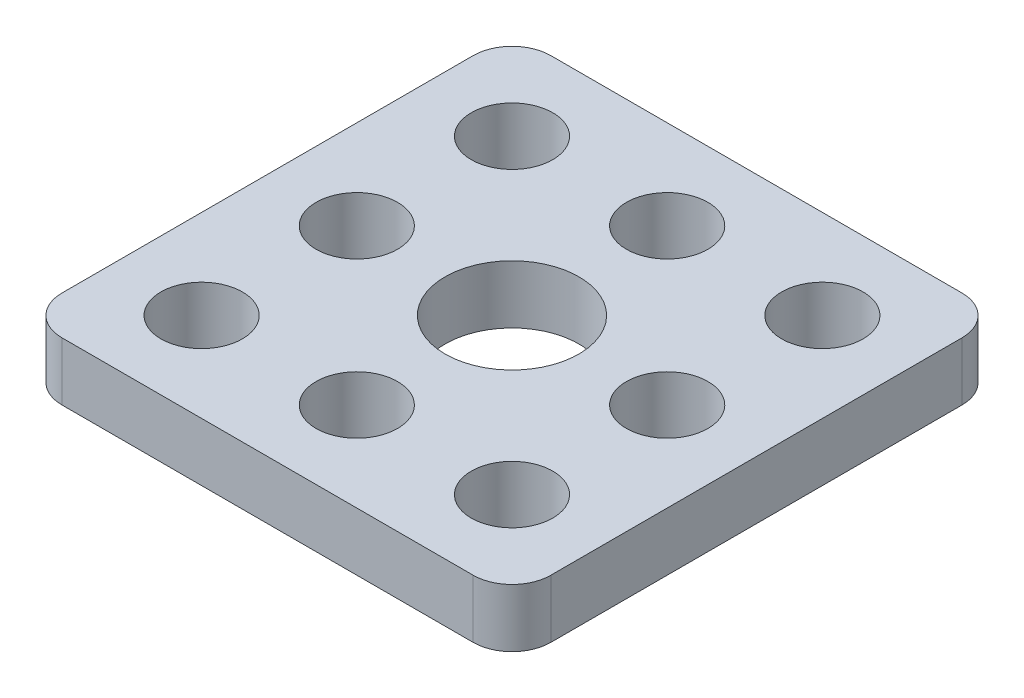
SolidWorks part; units mm, degrees
ref_plane "Front Plane" through (0, 0, 0) normal (0, 0, 1) x (1, 0, 0)
ref_plane "Top Plane" through (0, 0, 0) normal (0, 1, 0) x (1, 0, 0)
ref_plane "Right Plane" through (0, 0, 0) normal (1, 0, 0) x (0, 0, -1)
sketch "Sketch1" plane through (0, 0, 0) normal (0, 1, 0) x (1, 0, 0)
  line L0 (4.6, 20.6) -> (20.6, 20.6) construction
  line L1 (0, 0) -> (25.2, 0)
  line L2 (0, 0) -> (0, 25.2)
  line L3 (0, 25.2) -> (25.2, 25.2)
  line L4 (25.2, 0) -> (25.2, 25.2)
  line L5 (20.6, 20.6) -> (20.6, 4.6) construction
  line L6 (20.6, 4.6) -> (4.6, 4.6) construction
  line L7 (4.6, 4.6) -> (4.6, 20.6) construction
  circle A0 centre (4.6, 4.6) radius 2.1
  circle A1 centre (12.6, 4.6) radius 2.1
  circle A2 centre (20.6, 4.6) radius 2.1
  circle A3 centre (4.6, 12.6) radius 2.1
  circle A4 centre (4.6, 20.6) radius 2.1
  circle A5 centre (20.6, 12.6) radius 2.1
  circle A6 centre (20.6, 20.6) radius 2.1
  circle A7 centre (12.6, 20.6) radius 2.1
  circle A8 centre (12.6, 12.6) radius 3.45
  point P21 (0, 0)
  point P22 (0, 12.6)
  point P23 (0, 0)
  point P24 (12.6, 0)
  dimension "D2" = 4.2
  dimension "D8" = 6.9
  dimension "D1" = 16
  dimension "D3" = 16
  dimension "D4" = 2.5
  dimension "D5" = 2.5
  dimension "D6" = 2.5
  dimension "D7" = 2.5
extrude "Boss-Extrude1" add sketch "Sketch1" along normal blind 3
fillet "Fillet1" radius 2 4 edges at (25.2, 1.5, 0) (0, 1.5, 0) (0, 1.5, -25.2) (25.2, 1.5, -25.2)
equation "\"width\"= 24"
equation "\"thk\"= 3"
equation "\"holesize\"= 4.1"
equation "\"holedistance\"= ( 20 + 12 ) / 2"
equation "\"threaded_hole\"= 3.9"
equation "\"fillet_radius\"= 2"
equation "\"ground_clearance\"= 25"
equation "\"tire_thk\"= 4"
equation "\"innerwheel_diam\" = \"wheel_diam\"-2*\"tire_thk\""
equation "\"innerwheel_thk\"= 8"
equation "\"wheel_diam\"= 2*(\"width\"/2+\"ground_clearance\")"
equation "\"D1@Boss-Extrude1\"=\"thk\""
equation "\"xnum\"= 3'Number of holes in x"
equation "\"ynum\"= 3'Number of holes in y"
equation "\"D1@Sketch1\"=\"holedistance\""
equation "\"D2@Sketch1\"=\"holesize\"+0.1"
equation "\"D3@Sketch1\"=\"holedistance\""
equation "\"D5@Sketch1\"=\"D4@Sketch1\""
equation "\"D6@Sketch1\"=\"D4@Sketch1\""
equation "\"D7@Sketch1\"=\"D4@Sketch1\""
equation "\"D1@Fillet1\"=\"fillet_radius\""
